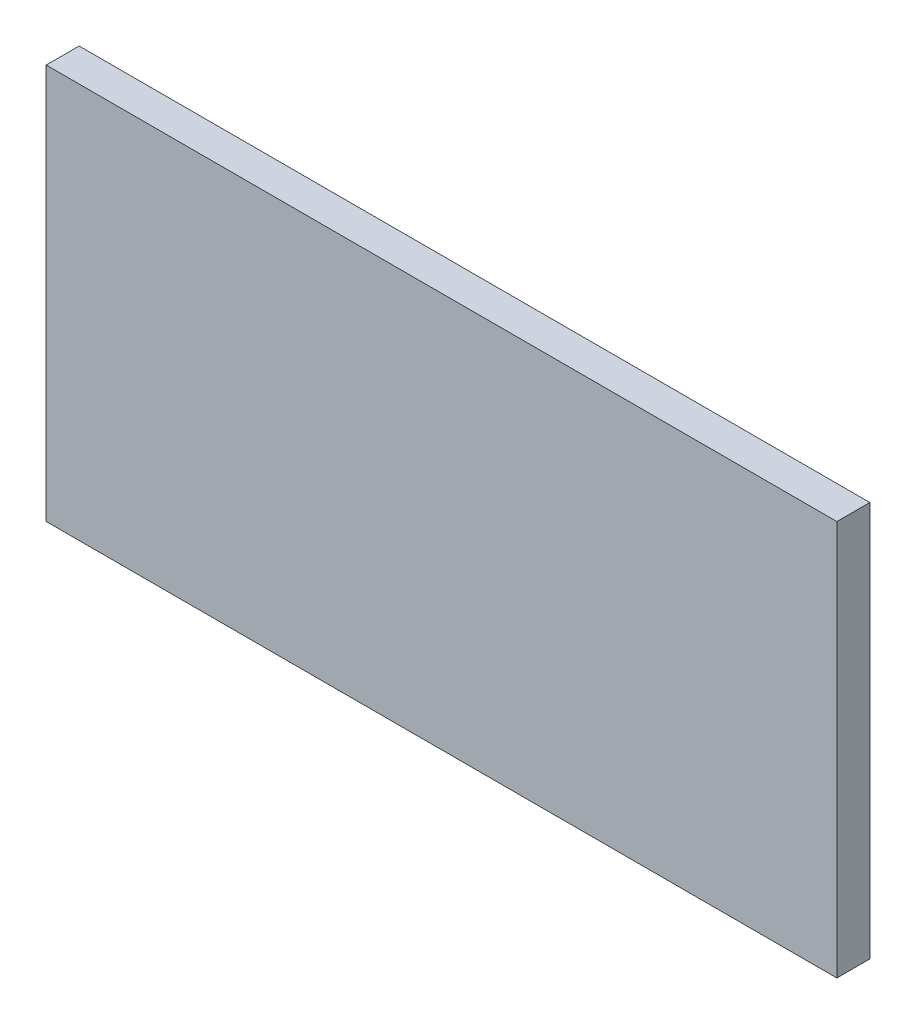
SolidWorks part; units mm, degrees
ref_plane "Front Plane" through (0, 0, 0) normal (0, 0, 1) x (1, 0, 0)
ref_plane "Top Plane" through (0, 0, 0) normal (0, 1, 0) x (1, 0, 0)
ref_plane "Right Plane" through (0, 0, 0) normal (1, 0, 0) x (0, 0, -1)
sketch "Sketch1" plane through (0, 0, 0) normal (0, 0, 1) x (1, 0, 0)
  line L1 (0, 0) -> (304.8, 0)
  line L2 (0, 0) -> (0, -152.4)
  line L3 (0, -152.4) -> (304.8, -152.4)
  line L4 (304.8, 0) -> (304.8, -152.4)
  dimension "D1" = 304.8
  dimension "D2" = 152.4
extrude "Boss-Extrude1" add sketch "Sketch1" along normal blind 12.7
